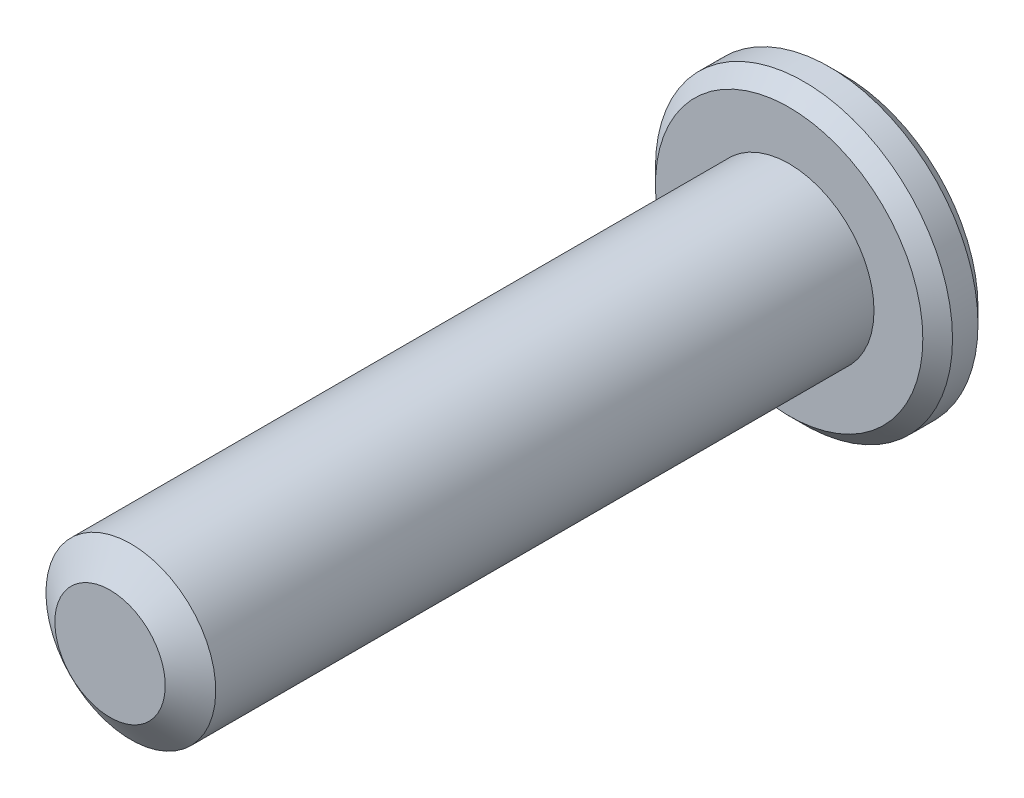
SolidWorks part; units mm, degrees
other "DetailItem1"
material "Alloy Steel"
ref_plane "Front Plane" through (0, 0, 0) normal (0, 0, 1) x (1, 0, 0)
ref_plane "Top Plane" through (0, 0, 0) normal (0, 1, 0) x (1, 0, 0)
ref_plane "Right Plane" through (0, 0, 0) normal (1, 0, 0) x (0, 0, -1)
sketch "Sketch0" plane through (0, 0, 0) normal (1, 0, 0) x (0, 0, -1)
  line L0 (0, 0) -> (-17.3, 0) construction
  line L1 (0, 3.5) -> (0, -3.5) construction
  line L2 (0, 3.5) -> (-1.3, 3.5) construction
  line L3 (-17.3, 0) -> (-17.3, 2) construction
  line L4 (-17.3, 2) -> (-16.6, 2) construction
  point P3 (0, 1.25)
  point P6 (0, 0)
  dimension "Head Diameter" = 7
  dimension "Drive Size" = 2.5
  dimension "Head Height" = 1.3
  dimension "Pitch" = 0.7
  dimension "Thread Size" = 4
  dimension "Length" = 16
sketch "Sketch1" plane through (0, 0, 0) normal (0, 0, 1) x (1, 0, 0)
  circle A0 centre (0, 0) radius 2
extrude "Extrude1" add sketch "Sketch1" along normal up to vertex (17.3 mm away) up to point (0, 0, 17.3)
sketch "Sketch4" plane through (0, 0, 0) normal (1, 0, 0) x (0, 0, -1)
  line L0 (-16.8099, 2) -> (-17.3, 1.3)
  line L1 (-17.3, 1.3) -> (-17.3, 2)
  line L2 (-16.8099, 2) -> (-17.3, 2)
  line L4 (0, 0) -> (-17.3, 0) construction
  dimension "D1" = 55
  dimension "D2" = 0.7
revolve "Cut-Revolve1" cut sketch "Sketch4" angle 360 about L4
sketch "Sketch6" plane through (0, 0, 0) normal (0, 0, 1) x (1, 0, 0)
  circle A0 centre (0, 0) radius 3.5
extrude "Extrude2" add sketch "Sketch6" along normal up to vertex (1.3 mm away) up to point (0, 3.5, 1.3)
sketch "Sketch7" plane through (0, 0, 0) normal (0, 0, 1) x (1, 0, 0)
  line L1 (0, 1.4434) -> (-1.25, 0.7217)
  line L2 (-1.25, 0.7217) -> (-1.25, -0.7217)
  line L3 (-1.25, -0.7217) -> (0, -1.4434)
  line L4 (0, -1.4434) -> (1.25, -0.7217)
  line L5 (1.25, -0.7217) -> (1.25, 0.7217)
  line L6 (1.25, 0.7217) -> (0, 1.4434)
  circle A0 centre (0, 0) radius 1.25 construction
extrude "Cut-Extrude1" cut sketch "Sketch7" along normal blind 0.975
sketch "Sketch8" plane through (0, 0, 0) normal (0, 0, 1) x (1, 0, 0)
  circle A0 centre (0, 0) radius 1.4434
extrude "Cut-Extrude2" cut sketch "Sketch8" along normal up to next (0.975 mm away) draft 45
chamfer "Chamfer1" distance 0.35 angle 45 2 edges at (3.5, 0, 1.3) (3.5, 0, 0)
sketch "For Drawing" [suppressed] plane through (0, 0, 0) normal (1, 0, 0) x (0, 0, -1)
  line L0 (-17.3, 2) -> (-17.3, -2) construction
  line L1 (-15.55, 2) -> (-15.55, -2) construction
  dimension "D1" = 1.75
ref_axis "Center Axis 1" [suppressed] through (0, 0, 0) along (0, 0, 1)
split "Split1" [suppressed] bodies to split 107
sketch "Sketch2" [suppressed] plane through (0, 0, 17.3) normal (0, 0, -1) x (-1, 0, 0)
  circle A1 centre (0, 0) radius 2
curve "Helix/Spiral1" [suppressed] pitch 0.7 height 16.7 turns 23.8571 parameters "pitch"=0.7
sketch "Sketch3" [suppressed] plane through (0, 0, 0) normal (1, 0, 0) x (0, 0, -1)
  line L0 (-17.9125, 2) -> (-17.65, 1.5453)
  line L1 (-17.65, 1.5453) -> (-17.5625, 1.5453)
  line L2 (-17.5625, 1.5453) -> (-17.3, 2)
  line L3 (-17.9125, 2) -> (-17.3, 2)
  line L4 (-17.6063, 2) -> (-17.6063, 1.5453) construction
  line L5 (-17.7813, 1.7727) -> (-17.4313, 1.7727) construction
  dimension "D1" = 0.0875
  dimension "D2" = 0.35
  dimension "D3" = 60
sweep "Cut-Sweep1" [suppressed] cut profiles "Sketch3" path "Helix/Spiral1"
combine bodies "Combine1" [suppressed] operation type add bodies to combine 102 111
equation "\"D3@Helix/Spiral1\"=\"Length@Sketch0\"+\"Pitch@Sketch0\""
equation "\"D1@Sketch3\" = \"Pitch@Sketch0\" * .125"
equation "\"D2@Sketch3\" = \"Pitch@Sketch0\" * .5"
equation "\"D1@Cut-Extrude1\"=\"Head Height@Sketch0\"*.75"
equation "\"D1@Chamfer1\"= \"Head Diameter@Sketch0\" * .05"
equation "\"D1@For Drawing\" = \"Pitch@Sketch0\" * 2.5"
equation "\"pitch@Helix/Spiral1\"=\"Pitch@Sketch0\""
equation "\"D2@Sketch4\"=\"Pitch@Sketch0\""
